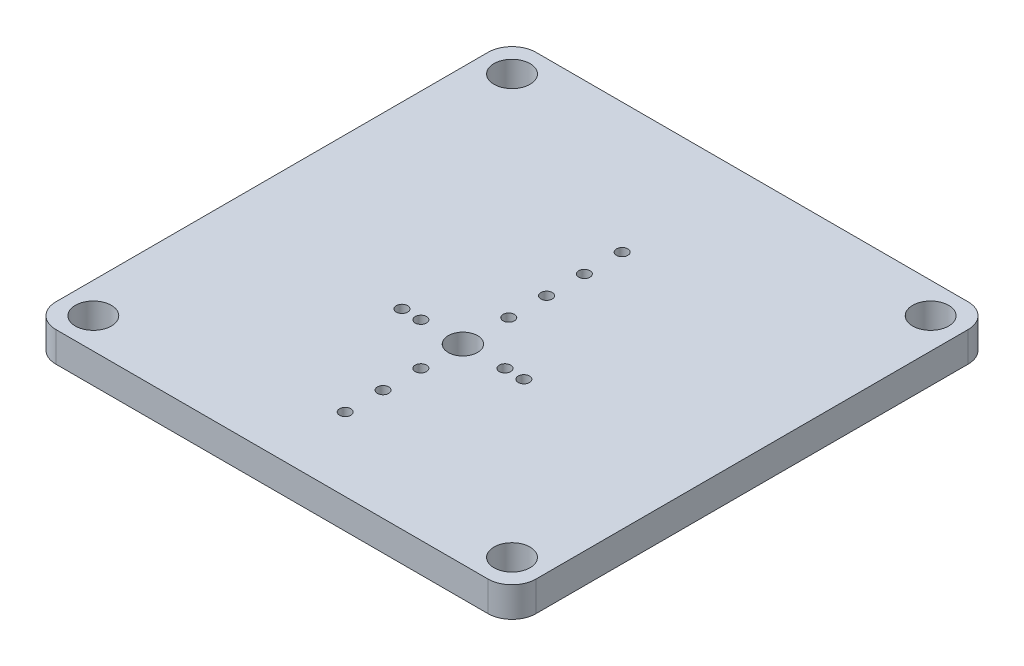
SolidWorks part; units mm, degrees
material "ABS PC"
ref_plane "Front Plane" through (0, 0, 0) normal (0, 0, 1) x (1, 0, 0)
ref_plane "Top Plane" through (0, 0, 0) normal (0, 1, 0) x (1, 0, 0)
ref_plane "Right Plane" through (0, 0, 0) normal (1, 0, 0) x (0, 0, -1)
sketch "Sketch1" plane through (0, 0, 0) normal (0, 1, 0) x (1, 0, 0)
  line L0 (0, 50.8) -> (3.2513, 47.5487)
  line L1 (0, 0) -> (50.8, 0)
  line L2 (0, 0) -> (0, 50.8)
  line L3 (0, 50.8) -> (50.8, 50.8)
  line L4 (50.8, 0) -> (50.8, 50.8)
  line L5 (0, 25.4) -> (50.8, 25.4) construction
  line L6 (25.4, 50.8) -> (25.4, 0) construction
  circle A0 centre (3.2513, 47.5487) radius 1.905
  circle A1 centre (3.2513, 3.2513) radius 1.905
  circle A2 centre (47.5487, 3.2513) radius 1.905
  circle A3 centre (47.5487, 47.5487) radius 1.905
  circle A4 centre (25.404, 11.752) radius 0.6 construction
  circle A5 centre (18.954, 20.202) radius 0.6 construction
  circle A6 centre (20.954, 20.202) radius 0.6 construction
  circle A7 centre (31.854, 20.202) radius 0.6 construction
  circle A8 centre (29.854, 20.202) radius 0.6 construction
  circle A9 centre (25.404, 37.052) radius 0.6 construction
  circle A10 centre (25.404, 33.052) radius 0.6 construction
  circle A11 centre (25.404, 29.052) radius 0.6 construction
  circle A12 centre (25.404, 25.052) radius 0.6 construction
  circle A13 centre (25.404, 7.752) radius 0.6 construction
  circle A14 centre (25.404, 15.752) radius 0.6 construction
  circle A15 centre (25.404, 20.202) radius 1.55 construction
  circle A16 centre (25.404, 11.752) radius 0.6
  circle A17 centre (18.954, 20.202) radius 0.6
  circle A18 centre (20.954, 20.202) radius 0.6
  circle A19 centre (31.854, 20.202) radius 0.6
  circle A20 centre (29.854, 20.202) radius 0.6
  circle A21 centre (25.404, 37.052) radius 0.6
  circle A22 centre (25.404, 33.052) radius 0.6
  circle A23 centre (25.404, 29.052) radius 0.6
  circle A24 centre (25.404, 25.052) radius 0.6
  circle A25 centre (25.404, 7.752) radius 0.6
  circle A26 centre (25.404, 15.752) radius 0.6
  circle A27 centre (25.404, 20.202) radius 1.55
  dimension "D1" = 3.81
  dimension "D2" = 50.8
  dimension "D3" = 50.8
extrude "Boss-Extrude1" add sketch "Sketch1" along normal blind 3.175 contours A0 L2 L1 L4 L3 A1 A2 A3 region at (25.4, 0, -50.0816)
sketch "Sketch2" plane through (0, 0, 0) normal (0, 1, 0) x (1, 0, 0)
  line L0 (3.2513, 44.2975) -> (3.2513, 6.5025)
  line L1 (6.5025, 3.2513) -> (44.2975, 3.2513)
  line L2 (47.5487, 44.2975) -> (47.5487, 6.5025)
  line L3 (44.2975, 47.5487) -> (6.5025, 47.5487)
  circle A0 centre (3.2513, 47.5487) radius 1.905
  circle A1 centre (3.2513, 47.5487) radius 3.2513
  circle A2 centre (47.5487, 47.5487) radius 1.905
  circle A3 centre (47.5487, 47.5487) radius 3.2513
  circle A4 centre (47.5487, 3.2513) radius 1.905
  circle A5 centre (47.5487, 3.2513) radius 3.2513
  circle A6 centre (3.2513, 3.2513) radius 1.905
  circle A7 centre (3.2513, 3.2513) radius 3.2513
extrude "Cut-Extrude1" [suppressed] cut sketch "Sketch2" along normal blind 1.5875 from surface contours A7 L1 A5 L2 A3 L3 A1 L0 starting at face at (3.2513, 0, -45.6437)
sketch "Sketch3" plane through (0, 0, 0) normal (0, 1, 0) x (1, 0, 0)
  line L0 (3.2513, 44.2975) -> (3.2513, 6.5025)
  line L1 (6.5025, 3.2513) -> (44.2975, 3.2513)
  line L2 (47.5487, 44.2975) -> (47.5487, 6.5025)
  line L3 (44.2975, 47.5487) -> (6.5025, 47.5487)
  circle A0 centre (3.2513, 47.5487) radius 1.905
  circle A1 centre (3.2513, 47.5487) radius 3.2513
  circle A2 centre (47.5487, 47.5487) radius 1.905
  circle A3 centre (47.5487, 47.5487) radius 3.2513
  circle A4 centre (47.5487, 3.2513) radius 1.905
  circle A5 centre (47.5487, 3.2513) radius 3.2513
  circle A6 centre (3.2513, 3.2513) radius 1.905
  circle A7 centre (3.2513, 3.2513) radius 3.2513
extrude "Cut-Extrude2" [suppressed] cut sketch "Sketch3" against normal blind 1.5875 from surface contours A7 L1 A5 L2 A3 L3 A1 L0 starting at face at (3.2513, 3.175, -45.6437)
fillet "Fillet1" radius 2.54 4 edges at (50.8, 1.5875, -50.8) (50.8, 1.5875, 0) (0, 1.5875, 0) (0, 1.5875, -50.8)
